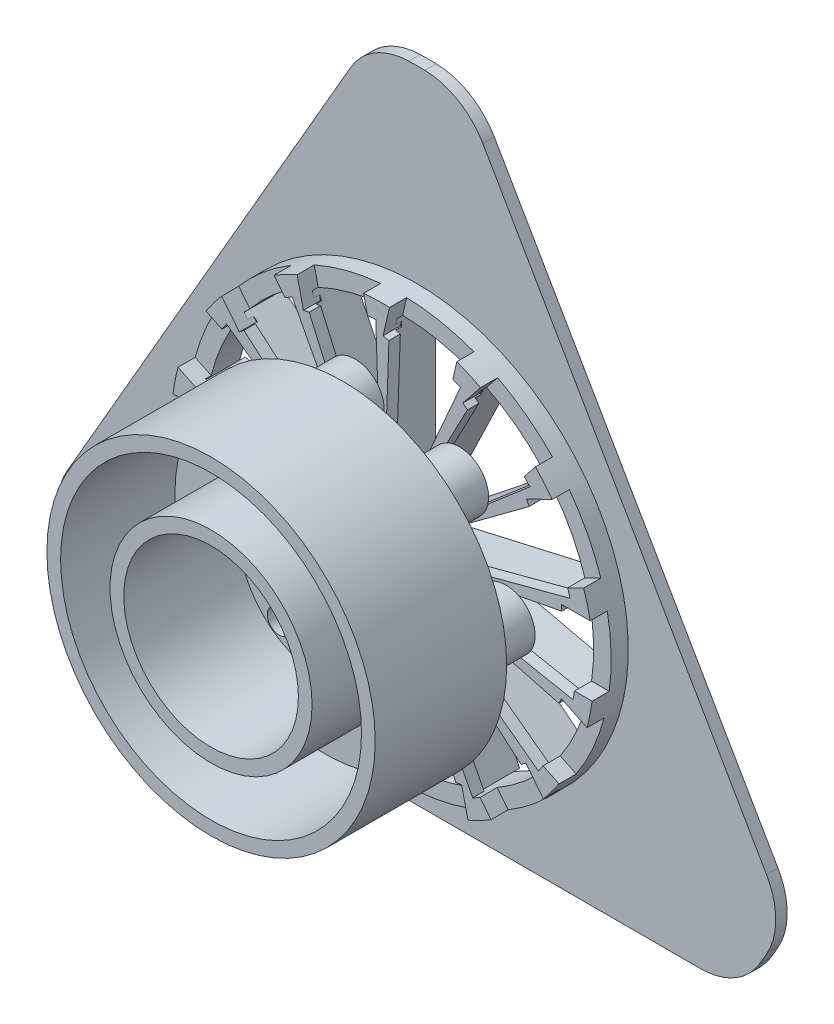
SolidWorks part; units mm, degrees
ref_plane "Спереди" through (0, 0, 0) normal (0, 0, 1) x (1, 0, 0)
ref_plane "Сверху" through (0, 0, 0) normal (0, 1, 0) x (1, 0, 0)
ref_plane "Справа" through (0, 0, 0) normal (1, 0, 0) x (0, 0, -1)
sketch "Sketch1" plane through (0, 0, 0) normal (0, 0, 1) x (1, 0, 0)
  line L0 (3.9, 6.755) -> (7.8, 0) construction
  line L2 (5.85, 10.1325) -> (11.7, 0) construction
  line L4 (7.8, 13.51) -> (15.6, 0) construction
  circle A61 centre (0, 0) radius 20
  circle A131 centre (0, 0) radius 1.25
  circle A484 centre (3.9, 0) radius 1.25
  circle A485 centre (7.8, 0) radius 1.25
  circle A486 centre (11.7, 0) radius 1.25
  circle A487 centre (15.6, 0) radius 1.25
  circle A488 centre (1.95, -3.3775) radius 1.25
  circle A489 centre (3.9, -6.755) radius 1.25
  circle A490 centre (5.85, -10.1325) radius 1.25
  circle A491 centre (7.8, -13.51) radius 1.25
  circle A492 centre (-1.95, -3.3775) radius 1.25
  circle A493 centre (-3.9, -6.755) radius 1.25
  circle A494 centre (-5.85, -10.1325) radius 1.25
  circle A495 centre (-7.8, -13.51) radius 1.25
  circle A496 centre (-3.9, 0) radius 1.25
  circle A497 centre (-7.8, 0) radius 1.25
  circle A498 centre (-11.7, 0) radius 1.25
  circle A499 centre (-15.6, 0) radius 1.25
  circle A500 centre (-1.95, 3.3775) radius 1.25
  circle A501 centre (-3.9, 6.755) radius 1.25
  circle A502 centre (-5.85, 10.1325) radius 1.25
  circle A503 centre (-7.8, 13.51) radius 1.25
  circle A504 centre (1.95, 3.3775) radius 1.25
  circle A505 centre (3.9, 6.755) radius 1.25
  circle A506 centre (5.85, 10.1325) radius 1.25
  circle A507 centre (7.8, 13.51) radius 1.25
  circle A508 centre (5.85, 3.3775) radius 1.25
  circle A509 centre (7.8, 6.755) radius 1.25
  circle A510 centre (9.75, 3.3775) radius 1.25
  circle A511 centre (11.7, 6.755) radius 1.25
  circle A512 centre (9.7491, 10.1341) radius 1.25
  circle A513 centre (13.6509, 3.3759) radius 1.25
  circle A514 centre (5.85, -3.3791) radius 1.25
  circle A515 centre (9.75, -3.3791) radius 1.25
  circle A516 centre (7.8, -6.7566) radius 1.25
  circle A517 centre (11.7, -6.7566) radius 1.25
  circle A518 centre (9.7491, -10.1356) radius 1.25
  circle A519 centre (13.6509, -3.3775) radius 1.25
  circle A520 centre (-0.0013, -6.7573) radius 1.25
  circle A521 centre (1.9487, -10.1348) radius 1.25
  circle A522 centre (-1.9513, -10.1348) radius 1.25
  circle A523 centre (-0.0013, -13.5123) radius 1.25
  circle A524 centre (-3.9032, -13.5123) radius 1.25
  circle A525 centre (3.9005, -13.5123) radius 1.25
  circle A526 centre (-5.8527, -3.3791) radius 1.25
  circle A527 centre (-7.8027, -6.7566) radius 1.25
  circle A528 centre (-9.7527, -3.3791) radius 1.25
  circle A529 centre (-11.7027, -6.7566) radius 1.25
  circle A530 centre (-13.6536, -3.3775) radius 1.25
  circle A531 centre (-9.7518, -10.1356) radius 1.25
  circle A532 centre (-5.8527, 3.3775) radius 1.25
  circle A533 centre (-9.7527, 3.3775) radius 1.25
  circle A534 centre (-7.8027, 6.755) radius 1.25
  circle A535 centre (-11.7027, 6.755) radius 1.25
  circle A536 centre (-9.7518, 10.1341) radius 1.25
  circle A537 centre (-13.6536, 3.3759) radius 1.25
  circle A538 centre (-0.0014, 6.7558) radius 1.25
  circle A539 centre (-1.9514, 10.1333) radius 1.25
  circle A540 centre (1.9486, 10.1333) radius 1.25
  circle A541 centre (-0.0014, 13.5108) radius 1.25
  circle A542 centre (3.9005, 13.5108) radius 1.25
  circle A543 centre (-3.9032, 13.5108) radius 1.25
  circle A544 centre (13.65, -1.1258) radius 2.2517 construction
  circle A545 centre (11.7009, -4.5044) radius 2.2522 construction
  circle A546 centre (9.75, -7.8834) radius 2.2522 construction
  circle A547 centre (7.7987, -11.2591) radius 2.2509 construction
  circle A548 centre (13.65, -1.1258) radius 0.65
  circle A549 centre (11.7009, -4.5044) radius 0.65
  circle A550 centre (9.75, -7.8834) radius 0.65
  circle A551 centre (7.7987, -11.2591) radius 0.65
  circle A552 centre (9.75, -1.1258) radius 0.65
  circle A553 centre (7.8009, -4.5044) radius 0.65
  circle A554 centre (5.85, -7.8834) radius 0.65
  circle A555 centre (3.8987, -11.2591) radius 0.65
  circle A556 centre (5.85, -1.1258) radius 0.65
  circle A557 centre (3.9009, -4.5044) radius 0.65
  circle A558 centre (1.95, -7.8834) radius 0.65
  circle A559 centre (-0.0013, -11.2591) radius 0.65
  circle A560 centre (1.95, -1.1258) radius 0.65
  circle A561 centre (0.0009, -4.5044) radius 0.65
  circle A562 centre (-1.95, -7.8834) radius 0.65
  circle A563 centre (-3.9013, -11.2591) radius 0.65
  circle A564 centre (-1.95, -1.1258) radius 0.65
  circle A565 centre (-3.8991, -4.5044) radius 0.65
  circle A566 centre (-5.85, -7.8834) radius 0.65
  circle A567 centre (-7.8013, -11.2591) radius 0.65
  circle A568 centre (-5.85, -1.1258) radius 0.65
  circle A569 centre (-7.7991, -4.5044) radius 0.65
  circle A570 centre (-9.75, -7.8834) radius 0.65
  circle A572 centre (-9.75, -1.1258) radius 0.65
  circle A573 centre (-11.6991, -4.5044) radius 0.65
  circle A576 centre (-13.65, -1.1258) radius 0.65
  circle A587 centre (0, 2.2517) radius 2.2517 construction
  circle A588 centre (0, 2.2517) radius 0.65
  circle A589 centre (3.9, 2.2517) radius 0.65
  circle A590 centre (7.8, 2.2517) radius 0.65
  circle A591 centre (11.7, 2.2517) radius 0.65
  circle A592 centre (15.6, 2.2517) radius 0.65
  circle A593 centre (1.9491, 5.6297) radius 2.2522 construction
  circle A594 centre (1.9491, 5.6297) radius 0.65
  circle A595 centre (5.8491, 5.6297) radius 0.65
  circle A596 centre (9.7491, 5.6297) radius 0.65
  circle A597 centre (13.6491, 5.6297) radius 0.65
  circle A598 centre (3.8991, 9.0072) radius 2.2522 construction
  circle A599 centre (3.8991, 9.0072) radius 0.65
  circle A600 centre (7.7991, 9.0072) radius 0.65
  circle A601 centre (11.6991, 9.0072) radius 0.65
  circle A602 centre (5.85, 12.3842) radius 2.2517 construction
  circle A603 centre (5.85, 12.3842) radius 0.65
  circle A604 centre (9.75, 12.3842) radius 0.65
  circle A605 centre (5.85, -14.6358) radius 0.65
  circle A606 centre (1.9509, -14.6353) radius 0.65
  circle A607 centre (-1.9491, -14.6353) radius 0.65
  circle A608 centre (-5.85, -14.6358) radius 0.65
  circle A609 centre (-15.6, 2.2517) radius 0.65
  circle A610 centre (-13.65, 5.6281) radius 0.65
  circle A611 centre (-11.7, 9.0056) radius 0.65
  circle A612 centre (-9.75, 12.3842) radius 0.65
  circle A613 centre (-5.85, 12.3842) radius 0.65
  circle A614 centre (-1.95, 12.3842) radius 0.65
  circle A615 centre (1.95, 12.3842) radius 0.65
  circle A616 centre (-7.8, 9.0056) radius 0.65
  circle A617 centre (-9.75, 5.6281) radius 0.65
  circle A618 centre (-11.7, 2.2517) radius 0.65
  circle A619 centre (-3.9, 9.0056) radius 0.65
  circle A620 centre (-5.85, 5.6281) radius 0.65
  circle A621 centre (-7.8, 2.2517) radius 0.65
  circle A622 centre (0, 9.0056) radius 0.65
  circle A623 centre (-1.95, 5.6281) radius 0.65
  circle A624 centre (-3.9, 2.2517) radius 0.65
  circle A625 centre (-15.5991, -4.5044) radius 0.65
  circle A626 centre (-13.65, -7.8834) radius 0.65
  circle A627 centre (-17.55, -7.8834) radius 0.65
  circle A628 centre (-19.5013, -11.2591) radius 0.65
  circle A629 centre (-15.6013, -11.2591) radius 0.65
  circle A630 centre (-11.7013, -11.2591) radius 0.65
  point P51 (0, 0)
  point P125 (-0.0013, -0.0008)
  point P231 (0, 0)
  dimension "D1" = 5
  dimension "D3" = 6
  dimension "D5" = 8
  dimension "D7" = 4
  dimension "D11" = 4
  dimension "D2" = 6
  dimension "D6" = 5
  dimension "D8" = 3
  dimension "D9" = 2
  dimension "D4" = 1.3
  dimension "D10" = 3
ref_plane "Plane1" through (0, 0, 10) normal (0, 0, 1) x (1, 0, 0)
sketch "Sketch2" plane through (0, 0, 10) normal (0, 0, 1) x (1, 0, 0)
  line L0 (0, 15.7191) -> (0, 7.2245) construction
  line L62 (-0.15, 16.9697) -> (-0.15, 2.9962)
  line L71 (0.15, 16.9697) -> (0.15, 2.9962)
  line L92 (7.498, 15.2241) -> (1.4352, 2.6344)
  line L101 (7.2278, 15.3543) -> (1.1649, 2.7646)
  line L110 (13.361, 10.4632) -> (2.4361, 1.7509)
  line L119 (13.174, 10.6977) -> (2.249, 1.9854)
  line L124 (16.5777, 3.6299) -> (2.9545, 0.5205)
  line L133 (16.5109, 3.9224) -> (2.8877, 0.813)
  line L142 (16.5109, -3.9224) -> (2.8877, -0.813)
  line L151 (16.5777, -3.6299) -> (2.9545, -0.5205)
  line L160 (13.174, -10.6977) -> (2.249, -1.9854)
  line L165 (13.361, -10.4632) -> (2.4361, -1.7509)
  line L168 (7.2278, -15.3543) -> (1.1649, -2.7646)
  line L171 (7.498, -15.2241) -> (1.4352, -2.6344)
  line L174 (-0.15, -16.9697) -> (-0.15, -2.9962)
  line L177 (0.15, -16.9697) -> (0.15, -2.9962)
  line L180 (-7.498, -15.2241) -> (-1.4352, -2.6344)
  line L183 (-7.2278, -15.3543) -> (-1.1649, -2.7646)
  line L186 (-13.361, -10.4632) -> (-2.4361, -1.7509)
  line L189 (-13.174, -10.6977) -> (-2.249, -1.9854)
  line L192 (-16.5777, -3.6299) -> (-2.9545, -0.5205)
  line L193 (-16.5109, -3.9224) -> (-2.8877, -0.813)
  line L194 (-16.5109, 3.9224) -> (-2.8877, 0.813)
  line L195 (-16.5777, 3.6299) -> (-2.9545, 0.5205)
  line L196 (-13.174, 10.6977) -> (-2.249, 1.9854)
  line L197 (-13.361, 10.4632) -> (-2.4361, 1.7509)
  line L198 (-7.2278, 15.3543) -> (-1.1649, 2.7646)
  line L199 (-7.498, 15.2241) -> (-1.4352, 2.6344)
  circle A52 centre (0, 0) radius 16.9704
  circle A53 centre (0, 0) radius 18.5
  circle A199 centre (0, 0) radius 3
  point P62 (0, 0)
  dimension "D1" = 0.3
extrude "Boss-Extrude10" add sketch "Sketch2" along normal blind 4 contours A53 A52 | A199 L71 A52 L62 | A199 L92 A52 L101 | A199 L110 A52 L119 | A199 L124 A52 L133 | A199 L142 A52 L151 | A199 L160 A52 L165 | A199 L168 A52 L171 | A199 L174 A52 L177 | A199 L180 A52 L183 | A199 L186 A52 L189 | A199 L192 A52 L193 | A199 L196 A52 L197 | A199 L198 A52 L199 | A199 L194 A52 L195 | A199 region at (0, 9.9845, 10) region at (0, 0, 10) region at (-4.3321, 8.9957, 10) region at (4.3321, 8.9957, 10) region at (-7.8062, 6.2252, 10) region at (7.8062, 6.2252, 10) region at (-9.7341, 2.2218, 10) region at (9.7341, 2.2218, 10) region at (-9.7341, -2.2218, 10) region at (9.7341, -2.2218, 10) region at (-7.8062, -6.2252, 10) region at (7.8062, -6.2252, 10) region at (-4.3321, -8.9957, 10) region at (4.3321, -8.9957, 10) region at (0, -9.9845, 10) region at (-17.9767, 0, 10)
sketch "Sketch8" plane through (0, 0, 14) normal (0, 0, 1) x (1, 0, 0)
  circle A0 centre (0, 0) radius 21.2494
  circle A1 centre (0, 0) radius 22.6785
extrude "Boss-Extrude11" add sketch "Sketch8" against normal blind 4 separate body
sketch "Sketch9" plane through (0, 0, 14) normal (0, 0, 1) x (1, 0, 0)
  line L0 (-7.2278, 15.3543) -> (-1.1649, 2.7646) construction
  line L2 (13.361, 10.4632) -> (2.4361, 1.7509) construction
  line L3 (7.2278, 15.3543) -> (1.1649, 2.7646) construction
  line L7 (-13.361, 10.4632) -> (-2.4361, 1.7509) construction
  circle A0 centre (1.4743, 6.4592) radius 1.6243
  circle A1 centre (1.4743, 6.4592) radius 1.1243
  circle A2 centre (5.9692, 2.8746) radius 1.6243
  circle A3 centre (5.9692, 2.8746) radius 1.1243
  circle A4 centre (5.9692, -2.8746) radius 1.6243
  circle A5 centre (5.9692, -2.8746) radius 1.1243
  circle A6 centre (1.4743, -6.4592) radius 1.6243
  circle A7 centre (1.4743, -6.4592) radius 1.1243
  circle A8 centre (-4.1308, -5.1798) radius 1.6243
  circle A9 centre (-4.1308, -5.1798) radius 1.1243
  circle A10 centre (-6.6253, 0) radius 1.6243
  circle A11 centre (-6.6253, 0) radius 1.1243
  circle A12 centre (-4.1308, 5.1798) radius 1.6243
  circle A13 centre (-4.1308, 5.1798) radius 1.1243
  circle A14 centre (6.731, 8.4404) radius 2.5523
  circle A15 centre (6.731, 8.4404) radius 2.5523
  circle A16 centre (6.731, 8.4404) radius 2.0523
  circle A17 centre (10.7957, 0) radius 2.0523
  circle A18 centre (10.7957, 0) radius 2.5523
  circle A19 centre (6.731, -8.4404) radius 2.0523
  circle A20 centre (6.731, -8.4404) radius 2.5523
  circle A21 centre (-2.4023, -10.5251) radius 2.0523
  circle A22 centre (-2.4023, -10.5251) radius 2.5523
  circle A23 centre (-9.7266, -4.6841) radius 2.0523
  circle A24 centre (-9.7266, -4.6841) radius 2.5523
  circle A25 centre (-9.7266, 4.6841) radius 2.0523
  circle A26 centre (-9.7266, 4.6841) radius 2.5523
  circle A27 centre (-2.4023, 10.5251) radius 2.0523
  circle A28 centre (-2.4023, 10.5251) radius 2.5523
  point P24 (0, 0)
  point P51 (0, 0)
  dimension "D3" = 0.5
  dimension "D4" = 0.5
  dimension "D1" = 7
  dimension "D2" = 7
extrude "Boss-Extrude12" add sketch "Sketch9" along normal blind 5 contours A0 A1 | A14 A16 | A28 A27 | A12 A13 | A26 A25 | A10 A11 | A24 A23 | A8 A9 | A22 A21 | A20 A19 | A4 A5 | A6 A7 | A2 A3 | A18 A17 region at (-0.1041, 6.4592, 14) region at (4.3908, 2.8746, 14) region at (4.3908, -2.8746, 14) region at (-0.1041, -6.4592, 14) region at (-5.7091, -5.1798, 14) region at (-8.2036, 0, 14) region at (-5.7091, 5.1798, 14) region at (4.2509, 8.4404, 14) region at (8.3156, 0, 14) region at (4.2509, -8.4404, 14) region at (-4.8824, -10.5251, 14) region at (-12.2067, -4.6841, 14) region at (-12.2067, 4.6841, 14) region at (-4.8824, 10.5251, 14)
sketch "Sketch11" plane through (0, 0, 19) normal (0, 0, 1) x (1, 0, 0)
  circle A0 centre (0, 0) radius 8.1149
  circle A2 centre (0, 0) radius 4.8946
  circle A3 centre (0, 0) radius 14.3613
  circle M6 centre (10.7957, 0) radius 2.0523
  circle M7 centre (10.7957, 0) radius 2.5523
extrude "Boss-Extrude16" add sketch "Sketch11" against normal blind 1.5 contours A2 | A0 A2 | A3 A0 M7 | M6 region at (-7.8854, 0, 19) region at (0, 0, 19) region at (-13.9551, 0, 19) region at (10.7957, 0, 19)
sketch "Sketch12" plane through (0, 0, 19) normal (0, 0, 1) x (1, 0, 0)
  circle A0 centre (0, 0) radius 7.6379
  circle A1 centre (0, 0) radius 8.8379
  circle A2 centre (0, 0) radius 14.3613
  circle A3 centre (0, 0) radius 13.1613
  circle A6 centre (0, 0) radius 14.3613 construction
  dimension "D1" = 1.2
  dimension "D2" = 1.2
extrude "Boss-Extrude14" add sketch "Sketch12" along normal blind 10 contours A1 A0 | A2 A3 region at (-8.5879, 0, 19) region at (-13.9551, 0, 19)
sketch "Sketch13" plane through (0, 0, 19) normal (0, 0, 1) x (1, 0, 0)
  circle A0 centre (1.414, 6.3633) radius 1.0411
  circle A1 centre (5.8567, 2.8619) radius 1.0411
  circle A2 centre (5.8891, -2.7946) radius 1.0411
  circle A3 centre (1.4869, -6.3467) radius 1.0411
  circle A4 centre (-4.0349, -5.1196) radius 1.0411
  circle A5 centre (-6.5184, -0.0374) radius 1.0411
  circle A6 centre (-4.0934, 5.073) radius 1.0411
  circle A7 centre (-2.4023, 10.5251) radius 1.2212
  circle A8 centre (6.8199, 8.5519) radius 1.2212
  circle A9 centre (11.0272, 0.1115) radius 1.2212
  circle A10 centre (7.0513, -8.4404) radius 1.2212
  circle A11 centre (-2.1137, -10.664) radius 1.2212
  circle A12 centre (-9.5664, -4.8849) radius 1.2212
  circle A13 centre (-9.6949, 4.5451) radius 1.2212
  point P4 (1.414, 6.3633)
  point P17 (0, 0)
  point P32 (0.1602, -0.0366)
  dimension "D1" = 7
  dimension "D2" = 7
extrude "Cut-Extrude2" cut sketch "Sketch13" against normal blind 1.5
sketch "Sketch16" plane through (0, 0, 10) normal (0, 0, -1) x (-1, 0, 0)
  line L0 (0, 0) -> (-0.5923, 16.9601)
  line L1 (0, 0) -> (0.5923, 16.9601)
  line L2 (0, 0) -> (7.8923, 15.0235)
  line L3 (0, 0) -> (6.8251, 15.5375)
  line L4 (0, 0) -> (13.6292, 10.1114)
  line L5 (0, 0) -> (12.8907, 11.0375)
  line L6 (0, 0) -> (16.6666, 3.1966)
  line L7 (0, 0) -> (16.4031, 4.3514)
  line L8 (0, 0) -> (16.4031, -4.3514)
  line L9 (0, 0) -> (16.6666, -3.1966)
  line L10 (0, 0) -> (12.8907, -11.0375)
  line L11 (0, 0) -> (13.6292, -10.1114)
  line L12 (0, 0) -> (6.8251, -15.5375)
  line L13 (0, 0) -> (7.8923, -15.0235)
  line L14 (0, 0) -> (-0.5923, -16.9601)
  line L15 (0, 0) -> (0.5923, -16.9601)
  line L16 (0, 0) -> (-7.8923, -15.0235)
  line L17 (0, 0) -> (-6.8251, -15.5375)
  line L18 (0, 0) -> (-13.6292, -10.1114)
  line L19 (0, 0) -> (-12.8907, -11.0375)
  line L20 (0, 0) -> (-16.6666, -3.1966)
  line L21 (0, 0) -> (-16.4031, -4.3514)
  line L22 (0, 0) -> (-16.4031, 4.3514)
  line L23 (0, 0) -> (-16.6666, 3.1966)
  line L24 (0, 0) -> (-12.8907, 11.0375)
  line L25 (0, 0) -> (-13.6292, 10.1114)
  line L26 (0, 0) -> (-6.8251, 15.5375)
  line L27 (0, 0) -> (-7.8923, 15.0235)
  arc A0 (-0.15, 16.9697) -> (-7.2278, 15.3543) centre (0, 0) ccw construction
  arc A1 (7.2278, 15.3543) -> (0.15, 16.9697) centre (0, 0) ccw construction
  arc A2 (-0.5923, 16.9601) -> (0.5923, 16.9601) centre (0, 0) cw
  arc A3 (6.8251, 15.5375) -> (7.8923, 15.0235) centre (0, 0) cw
  arc A4 (12.8907, 11.0375) -> (13.6292, 10.1114) centre (0, 0) cw
  arc A5 (16.4031, 4.3514) -> (16.6666, 3.1966) centre (0, 0) cw
  arc A6 (16.6666, -3.1966) -> (16.4031, -4.3514) centre (0, 0) cw
  arc A7 (13.6292, -10.1114) -> (12.8907, -11.0375) centre (0, 0) cw
  arc A8 (7.8923, -15.0235) -> (6.8251, -15.5375) centre (0, 0) cw
  arc A9 (0.5923, -16.9601) -> (-0.5923, -16.9601) centre (0, 0) cw
  arc A10 (-6.8251, -15.5375) -> (-7.8923, -15.0235) centre (0, 0) cw
  arc A11 (-12.8907, -11.0375) -> (-13.6292, -10.1114) centre (0, 0) cw
  arc A12 (-16.4031, -4.3514) -> (-16.6666, -3.1966) centre (0, 0) cw
  arc A13 (-16.6666, 3.1966) -> (-16.4031, 4.3514) centre (0, 0) cw
  arc A14 (-13.6292, 10.1114) -> (-12.8907, 11.0375) centre (0, 0) cw
  arc A15 (-7.8923, 15.0235) -> (-6.8251, 15.5375) centre (0, 0) cw
  point P52 (0, 0)
  dimension "D1" = 14
extrude "Boss-Extrude17" add sketch "Sketch16" along normal blind 1 from surface contours A15 L27 L26 | A2 L0 L1 | A3 L3 L2 | A4 L5 L4 | A5 L7 L6 | A6 L9 L8 | A7 L11 L10 | A8 L13 L12 | A9 L15 L14 | A10 L17 L16 | A12 L21 L20 | A11 L19 L18 | A13 L23 L22 | A14 L25 L24 region at (0, 11.3113, 10) region at (-4.9078, 10.1911, 10) region at (-8.8435, 7.0525, 10) region at (-11.0277, 2.517, 10) region at (-11.0277, -2.517, 10) region at (-8.8435, -7.0525, 10) region at (-4.9078, -10.1911, 10) region at (0, -11.3113, 10) region at (4.9078, -10.1911, 10) region at (8.8435, -7.0525, 10) region at (11.0277, -2.517, 10) region at (11.0277, 2.517, 10) region at (8.8435, 7.0525, 10) region at (4.9078, 10.1911, 10) starting at face at (18.5, 0, 14)
ref_plane "Plane2" through (22.6785, 0, 0) normal (1, 0, 0) x (0, 0, -1)
sketch "Sketch17" plane through (22.6785, 0, 0) normal (1, 0, 0) x (0, 0, -1)
  line L0 (-14, 0.5205) -> (-10, 0.5205) construction
  line L1 (-14.4721, 3.5205) -> (-12.5, 3.5205)
  line L2 (-14.4721, 3.5205) -> (-14.4721, -2.4795)
  line L3 (-14.4721, -2.4795) -> (-12.5, -2.4795)
  line L4 (-12.5, 3.5205) -> (-12.5, -2.4795)
  line L5 (-14.4721, 3.5205) -> (-12.5, -2.4795) construction
  line L6 (-14.4721, -2.4795) -> (-12.5, 3.5205) construction
  line L7 (-10, -22.6785) -> (-10, 22.6785) construction
  point P0 (-13.4861, 0.5205)
  dimension "D1" = 2.5
extrude "Cut-Extrude4" cut sketch "Sketch17" against normal blind 5 from offset 2 offset against normal yes
pattern_circular "CirPattern1" count 14 over 360 of "Cut-Extrude4"
sketch "Sketch18" plane through (0, 0, 19) normal (0, 0, 1) x (1, 0, 0)
  circle A0 centre (0, 0) radius 21.2494
  circle A1 centre (0, 0) radius 22.6785
extrude "Cut-Extrude5" cut sketch "Sketch18" against normal through all both and the other way through all
sketch "Sketch19" plane through (0, 0, 10) normal (0, 0, -1) x (-1, 0, 0)
  circle A0 centre (0, 0) radius 18.5
  circle A1 centre (0, 0) radius 22.1002
extrude "Boss-Extrude18" add sketch "Sketch19" against normal blind 1
sketch "Sketch3" plane through (0, 0, 11) normal (0, 0, 1) x (1, 0, 0)
  circle A0 centre (0, 0) radius 21.3923
  circle A1 centre (0, 0) radius 35
extrude "Boss-Extrude2" add sketch "Sketch3" against normal blind 1 contours A1 region at (-34.0101, 0, 11)
sketch "Sketch4" plane through (0, 0, 10) normal (0, 0, -1) x (-1, 0, 0)
  circle A0 centre (0, 0) radius 29 construction
  circle A1 centre (0, 29) radius 2.9
  circle A2 centre (25.1147, -14.5) radius 2.9
  circle A3 centre (-25.1147, -14.5) radius 2.9
  point P11 (0, 0)
  dimension "D1" = 3
extrude "Boss-Extrude3" add sketch "Sketch4" along normal blind 2
sketch "Sketch6" plane through (0, 0, 10) normal (0, 0, 1) x (1, 0, 0)
  circle A0 centre (0, 30) radius 5
  circle A2 centre (25.9808, -15) radius 5
  circle A3 centre (-25.9808, -15) radius 5
  point P10 (0, 0)
  dimension "D1" = 3
extrude "Boss-Extrude4" add sketch "Sketch6" along normal blind 1
sketch "Sketch7" plane through (0, 0, 8) normal (0, 0, -1) x (-1, 0, 0)
  line L1 (0, 42) -> (-36.3731, -21)
  line L2 (-36.3731, -21) -> (36.3731, -21)
  line L3 (36.3731, -21) -> (0, 42)
  circle A2 centre (0, 0) radius 21 construction
  circle A3 centre (0, 0) radius 59.1314
extrude "Cut-Extrude1" cut sketch "Sketch7" against normal blind 10
fillet "Fillet1" radius 6 6 edges at (-4.1865, 34.7487, 10.5) (28, -21, 10.5) (-28, -21, 10.5) (4.1865, 34.7487, 10.5) (-32.1865, -13.7487, 10.5) (32.1865, -13.7487, 10.5)
sketch "Sketch20" plane through (0, 0, 10) normal (0, 0, 1) x (1, 0, 0)
  line L0 (0, 15.7191) -> (0, 7.2245) construction
  line L62 (-0.15, 16.9697) -> (-0.15, 0.6837)
  line L71 (0.15, 16.9697) -> (0.15, 0.6837)
  line L92 (7.498, 15.2241) -> (0.4318, 0.5509)
  line L101 (7.2278, 15.3543) -> (0.1615, 0.6811)
  line L110 (13.361, 10.4632) -> (0.6281, 0.309)
  line L119 (13.174, 10.6977) -> (0.441, 0.5436)
  line L124 (16.5777, 3.6299) -> (0.7, 0.0059)
  line L133 (16.5109, 3.9224) -> (0.6332, 0.2984)
  line L142 (16.5109, -3.9224) -> (0.6332, -0.2984)
  line L151 (16.5777, -3.6299) -> (0.7, -0.0059)
  line L160 (13.174, -10.6977) -> (0.441, -0.5436)
  line L165 (13.361, -10.4632) -> (0.6281, -0.309)
  line L168 (7.2278, -15.3543) -> (0.1615, -0.6811)
  line L171 (7.498, -15.2241) -> (0.4318, -0.5509)
  line L174 (-0.15, -16.9697) -> (-0.15, -0.6837)
  line L177 (0.15, -16.9697) -> (0.15, -0.6837)
  line L180 (-7.498, -15.2241) -> (-0.4318, -0.5509)
  line L183 (-7.2278, -15.3543) -> (-0.1615, -0.6811)
  line L186 (-13.361, -10.4632) -> (-0.6281, -0.309)
  line L189 (-13.174, -10.6977) -> (-0.441, -0.5436)
  line L192 (-16.5777, -3.6299) -> (-0.7, -0.0059)
  line L193 (-16.5109, -3.9224) -> (-0.6332, -0.2984)
  line L194 (-16.5109, 3.9224) -> (-0.6332, 0.2984)
  line L195 (-16.5777, 3.6299) -> (-0.7, 0.0059)
  line L196 (-13.174, 10.6977) -> (-0.441, 0.5436)
  line L197 (-13.361, 10.4632) -> (-0.6281, 0.309)
  line L198 (-7.2278, 15.3543) -> (-0.1615, 0.6811)
  line L199 (-7.498, 15.2241) -> (-0.4318, 0.5509)
  circle A52 centre (0, 0) radius 16.9704
  circle A53 centre (0, 0) radius 18.5
  circle A199 centre (0, 0) radius 0.7
  point P62 (0, 0)
  dimension "D1" = 0.3
extrude "Boss-Extrude19" add sketch "Sketch20" against normal blind 0.5 contours L71 A199 L62 A52 | L198 A199 L199 A52 | L196 A199 L197 A52 | L194 A199 L195 A52 | L192 A199 L193 A52 | L186 A199 L189 A52 | L180 A199 L183 A52 | L174 A199 L177 A52 | L168 A199 L171 A52 | L160 A199 L165 A52 | L142 A199 L151 A52 | L124 A199 L133 A52 | L92 A199 L101 A52 | L110 A199 L119 A52 region at (0, 8.8324, 10) region at (-3.8322, 7.9577, 10) region at (3.8322, 7.9577, 10) region at (-6.9054, 5.5069, 10) region at (6.9054, 5.5069, 10) region at (-8.6109, 1.9654, 10) region at (8.6109, 1.9654, 10) region at (-8.6109, -1.9654, 10) region at (8.6109, -1.9654, 10) region at (-6.9054, -5.5069, 10) region at (6.9054, -5.5069, 10) region at (-3.8322, -7.9577, 10) region at (3.8322, -7.9577, 10) region at (0, -8.8324, 10)
sketch "Sketch21" plane through (0, 0, 10) normal (0, 0, -1) x (-1, 0, 0)
  circle A0 centre (0, 0) radius 3
extrude "Boss-Extrude20" add sketch "Sketch21" along normal blind 0.5
